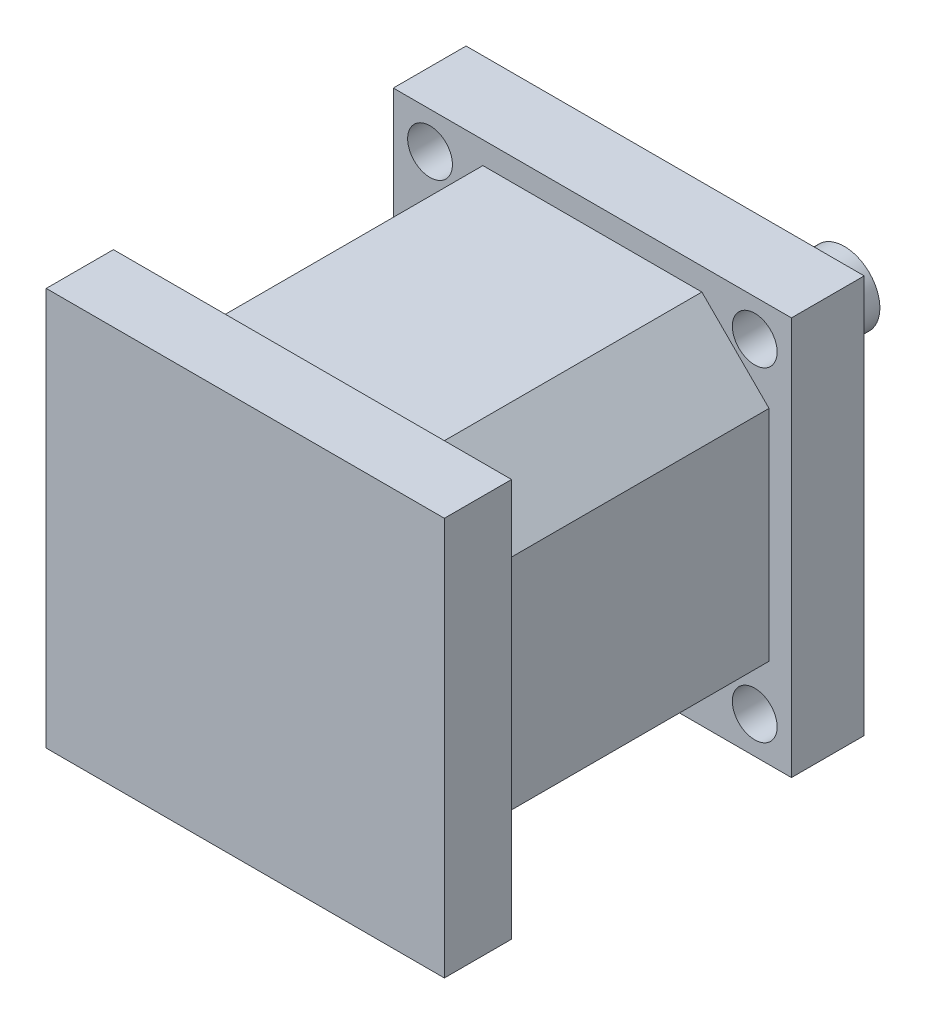
SolidWorks part; units mm, degrees
material "ABS"
ref_plane "Front Plane" through (0, 0, 0) normal (0, 0, 1) x (1, 0, 0)
ref_plane "Top Plane" through (0, 0, 0) normal (0, 1, 0) x (1, 0, 0)
ref_plane "Right Plane" through (0, 0, 0) normal (1, 0, 0) x (0, 0, -1)
sketch "Sketch1" plane through (0, 0, 0) normal (0, 0, 1) x (1, 0, 0)
  line L0 (21.15, 42.018) -> (21.15, -3.8447) construction
  line L1 (3.37, 2.8444) -> (38.93, 2.8444)
  line L2 (3.37, 2.8444) -> (3.37, 38.4044)
  line L3 (3.37, 38.4044) -> (38.93, 38.4044)
  line L4 (38.93, 2.8444) -> (38.93, 38.4044)
  line L5 (0, 20.6244) -> (51.3481, 20.6244) construction
  circle A4 centre (21.15, 20.6244) radius 11
  circle A5 centre (21.15, 20.6244) radius 2.5
  point P2 (3.37, 38.4044)
  dimension "D5" = 22
  dimension "D6" = 5
  dimension "D1" = 17.78
extrude "Boss-Extrude1" add sketch "Sketch1" along normal blind 4.5 contours L2 L1 L4 L3 A4 | A4 A5 | A5 region at (3.8729, 20.6244, 0) region at (10.4611, 20.6244, 0) region at (21.15, 20.6244, 0)
sketch "Sketch2" plane through (0, 0, 4.5) normal (0, 0, 1) x (1, 0, 0)
  line L8 (3.37, 38.4044) -> (3.37, 2.8444)
  line L10 (3.37, 2.8444) -> (38.93, 2.8444)
  line L12 (38.93, 2.8444) -> (38.93, 38.4044)
  line L14 (38.93, 38.4044) -> (3.37, 38.4044)
  line L16 (3.37, 38.4044) -> (3.37, 2.8444)
  line L18 (3.37, 2.8444) -> (38.93, 2.8444)
  line L20 (38.93, 2.8444) -> (38.93, 38.4044)
  line L22 (38.93, 38.4044) -> (3.37, 38.4044)
  dimension "D1" = 0
extrude "Boss-Extrude2" add sketch "Sketch2" along normal blind 2
sketch "Sketch5" plane through (0, 0, 0) normal (0, 0, -1) x (-1, 0, 0)
  line L0 (-38.93, 20.6244) -> (-3.37, 20.6244) construction
  line L1 (-21.15, 2.8444) -> (-21.15, 38.4044) construction
  line L8 (-3.37, 2.8444) -> (-3.37, 38.4044)
  line L10 (-3.37, 38.4044) -> (-38.93, 38.4044)
  line L12 (-38.93, 38.4044) -> (-38.93, 2.8444)
  line L14 (-38.93, 2.8444) -> (-3.37, 2.8444)
  line L16 (-3.37, 2.8444) -> (-3.37, 38.4044)
  line L18 (-3.37, 38.4044) -> (-38.93, 38.4044)
  line L20 (-38.93, 38.4044) -> (-38.93, 2.8444)
  line L22 (-38.93, 2.8444) -> (-3.37, 2.8444)
  circle A0 centre (-21.15, 20.6244) radius 11
  dimension "D2" = 22
  dimension "D1" = 0
extrude "Boss-Extrude5" add sketch "Sketch5" along normal blind 2 contours A0
sketch "Sketch6" plane through (0, 0, -2) normal (0, 0, -1) x (-1, 0, 0)
  line L0 (-32.15, 20.6244) -> (-10.15, 20.6244) construction
  line L1 (-21.15, 31.6244) -> (-21.15, 9.6244) construction
  circle A0 centre (-21.15, 20.6244) radius 3.175
  circle A1 centre (-21.15, 20.6244) radius 11
  circle A2 centre (-21.15, 20.6244) radius 11
  dimension "D2" = 6.35
  dimension "D1" = 0
extrude "Boss-Extrude6" add sketch "Sketch6" along normal blind 24 contours A0
sketch "Sketch7" plane through (0, 0, 0) normal (0, 0, -1) x (-1, 0, 0)
  line L0 (-38.93, 20.6244) -> (-3.37, 20.6244) construction
  line L1 (-21.15, 2.8444) -> (-21.15, 38.4044) construction
  line L8 (-3.37, 2.8444) -> (-3.37, 38.4044)
  line L10 (-3.37, 38.4044) -> (-38.93, 38.4044)
  line L12 (-38.93, 38.4044) -> (-38.93, 2.8444)
  line L14 (-38.93, 2.8444) -> (-3.37, 2.8444)
  line L16 (-3.37, 2.8444) -> (-3.37, 38.4044)
  line L18 (-3.37, 38.4044) -> (-38.93, 38.4044)
  line L20 (-38.93, 38.4044) -> (-38.93, 2.8444)
  line L22 (-38.93, 2.8444) -> (-3.37, 2.8444)
  circle A0 centre (-35.65, 6.1244) radius 2
  circle A1 centre (-6.65, 6.1244) radius 2
  circle A2 centre (-6.65, 35.1244) radius 2
  circle A3 centre (-35.65, 35.1244) radius 2
  dimension "D2" = 4
  dimension "D3" = 29
  dimension "D4" = 29
  dimension "D1" = 0
extrude "Cut-Extrude3" cut sketch "Sketch7" against normal blind 29 contours A0 | A3 | A2 | A1
sketch "Sketch8" plane through (0, 0, 6.5) normal (0, 0, 1) x (1, 0, 0)
  line L4 (3.37, 2.8444) -> (38.93, 2.8444)
  line L5 (38.93, 2.8444) -> (38.93, 38.4044)
  line L6 (38.93, 38.4044) -> (3.37, 38.4044)
  line L7 (3.37, 38.4044) -> (3.37, 2.8444)
  line L8 (3.37, 2.8444) -> (38.93, 2.8444)
  line L9 (38.93, 2.8444) -> (38.93, 38.4044)
  line L10 (38.93, 38.4044) -> (3.37, 38.4044)
  line L11 (3.37, 38.4044) -> (3.37, 2.8444)
  line L20 (5.37, 4.8444) -> (36.93, 4.8444)
  line L21 (36.93, 4.8444) -> (36.93, 36.4044)
  line L22 (36.93, 36.4044) -> (5.37, 36.4044)
  line L23 (5.37, 36.4044) -> (5.37, 4.8444)
  line L24 (5.37, 4.8444) -> (36.93, 4.8444)
  line L25 (36.93, 4.8444) -> (36.93, 36.4044)
  line L26 (36.93, 36.4044) -> (5.37, 36.4044)
  line L27 (5.37, 36.4044) -> (5.37, 4.8444)
  dimension "D1" = 0
  dimension "D2" = 2
extrude "Boss-Extrude7" add sketch "Sketch8" along normal blind 25 contours L24 L25 L26 L27
sketch "Sketch9" plane through (0, 0, 31.5) normal (0, 0, 1) x (1, 0, 0)
  line L4 (3.37, 2.8444) -> (38.93, 2.8444)
  line L5 (38.93, 2.8444) -> (38.93, 38.4044)
  line L6 (38.93, 38.4044) -> (3.37, 38.4044)
  line L7 (3.37, 38.4044) -> (3.37, 2.8444)
  line L8 (3.37, 2.8444) -> (38.93, 2.8444)
  line L9 (38.93, 2.8444) -> (38.93, 38.4044)
  line L10 (38.93, 38.4044) -> (3.37, 38.4044)
  line L11 (3.37, 38.4044) -> (3.37, 2.8444)
  dimension "D1" = 0
extrude "Boss-Extrude8" add sketch "Sketch9" along normal blind 6
chamfer "Chamfer1" distance 6 angle 45 4 edges at (5.37, 4.8444, 19) (36.93, 4.8444, 19) (36.93, 36.4044, 19) (5.37, 36.4044, 19)
scale "Scale1" scale about centroid uniform scaling yes scale factor 0.85
sketch "Sketch10" plane through (0, 0, -19.4258) normal (0, 0, -1) x (-1, 0, 0)
  circle A1 centre (-21.15, 20.6244) radius 2.6987
  circle A2 centre (-21.15, 20.6244) radius 2.6987
  dimension "D1" = 0
extrude "Cut-Extrude4" cut sketch "Sketch10" against normal blind 8.5
